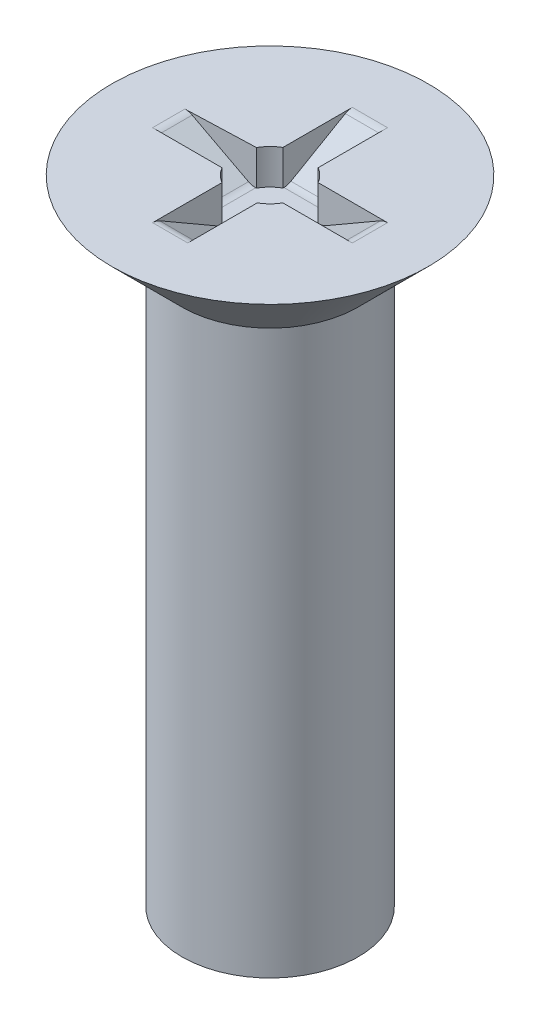
SolidWorks part; units mm, degrees
ref_plane "Front Plane" through (0, 0, 0) normal (0, 0, 1) x (1, 0, 0)
ref_plane "Top Plane" through (0, 0, 0) normal (0, 1, 0) x (1, 0, 0)
ref_plane "Right Plane" through (0, 0, 0) normal (1, 0, 0) x (0, 0, -1)
sketch "Sketch1" plane through (0, 0, 0) normal (0, 1, 0) x (1, 0, 0)
  circle A0 centre (0, 0) radius 1.25
  dimension "D1" = 2.5
extrude "Boss-Extrude1" add sketch "Sketch1" along normal blind 8
sketch "Sketch3" plane through (0, 8, 0) normal (0, 1, 0) x (1, 0, 0)
  circle A0 centre (0, 0) radius 2.25
  dimension "D1" = 4.5
extrude "Boss-Extrude2" add sketch "Sketch3" along normal blind 1
chamfer "Chamfer3" distance 1 angle 45 1 edges at (0, 8, 2.25)
sketch "Sketch4" plane through (0, 9, 0) normal (0, 1, 0) x (1, 0, 0)
  circle A0 centre (0, 0) radius 0.5
  dimension "D1" = 1
extrude "Cut-Extrude1" cut sketch "Sketch4" against normal blind 0.5
sketch "Sketch5" plane through (0, 0, 0) normal (0, 0, 1) x (1, 0, 0)
  line L0 (0, 9) -> (0, 8.5) construction
  line L1 (2.25, 9) -> (-2.25, 9) construction
  line L2 (0.5, 8.5) -> (-0.5, 8.5) construction
  line L3 (0, 8.5) -> (0.5, 8.5) construction
  line L4 (0.5, 8.5) -> (-0.5, 8.5) construction
  line L5 (0.5, 8.5) -> (1.366, 9)
  line L6 (1.366, 9) -> (0.5, 9)
  line L8 (0.5, 8.5) -> (0.25, 8.5)
  line L9 (0.25, 8.5) -> (0.25, 9)
  line L10 (0.5, 9) -> (-0.5, 9) construction
  line L11 (0.25, 9) -> (0.5, 9)
  dimension "D1" = 60
extrude "Cut-Extrude2" cut sketch "Sketch5" against normal mid plane 0.5 contours L11 L6 L5 L8 L9
pattern_circular "CirPattern1" count 4 every 90 about axis through (0, 0, 0) along (0, 1, 0) of "Cut-Extrude2"
draft "Draft1" type of draft neutral plane draft angle 2 faces to draft 1 face at (-0.683, 8.75, -0.25) neutral plane through (-0.25, 0, 0) neutral plane normal (1, 0, 0) parameters "D1"=2
fillet "Fillet4" radius 0.2 7 edges at (0.5, 8.5, 0) (1.366, 9, 0) (0, 8.5, -0.5) (0, 9, -1.366) (0, 9, 1.366) (-0.5, 8.5, 0.0044) (-1.366, 9, 0.0195)
